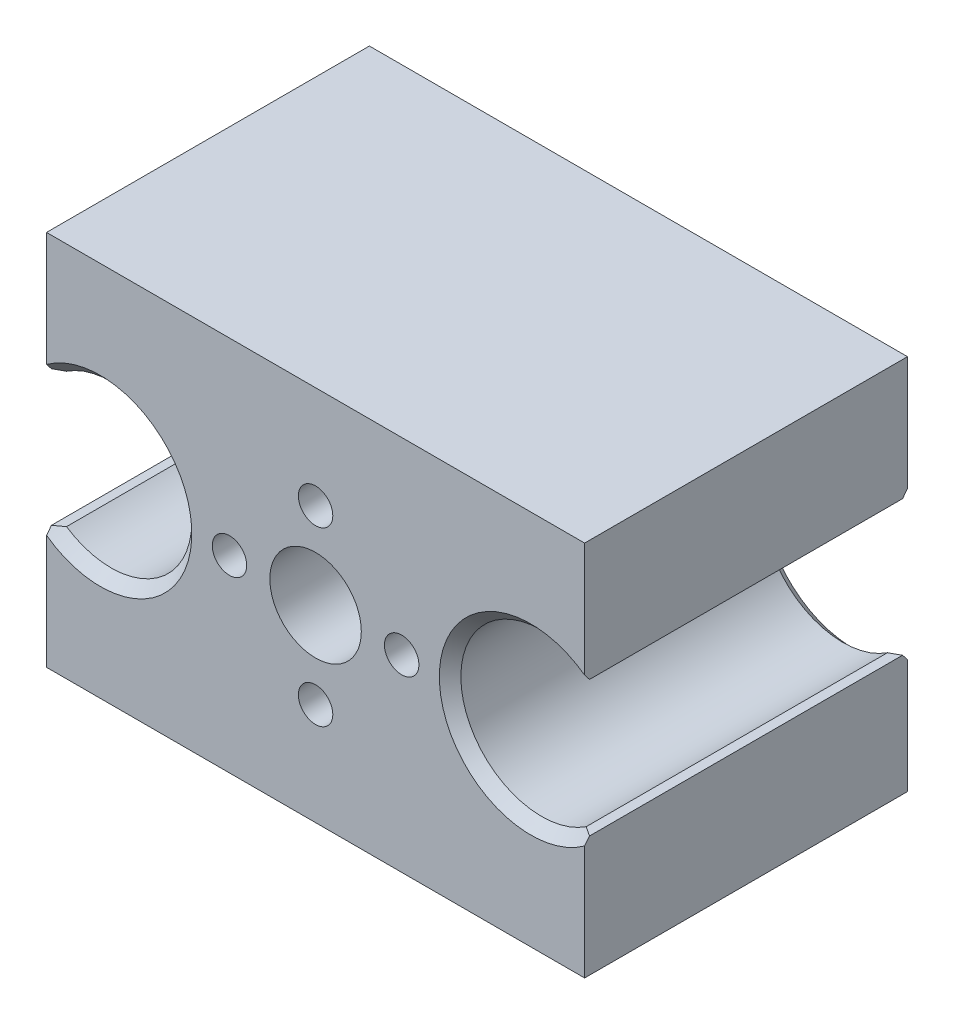
SolidWorks part; units mm, degrees
ref_plane "前视基准面" through (0, 0, 0) normal (0, 0, 1) x (1, 0, 0)
ref_plane "上视基准面" through (0, 0, 0) normal (0, 1, 0) x (1, 0, 0)
ref_plane "右视基准面" through (0, 0, 0) normal (1, 0, 0) x (0, 0, -1)
other "Configuration Table"
sketch "草图1" plane through (0, 0, 0) normal (0, 0, 1) x (1, 0, 0)
  line L1 (-25, -17.5) -> (25, -17.5)
  line L2 (-25, -17.5) -> (-25, 17.5)
  line L3 (-25, 17.5) -> (25, 17.5)
  line L4 (25, -17.5) -> (25, 17.5)
  line L5 (-25, -17.5) -> (25, 17.5) construction
  line L6 (-25, 17.5) -> (25, -17.5) construction
  point P0 (0, 0)
  dimension "D1" = 50
  dimension "D2" = 35
extrude "凸台-拉伸1" add sketch "草图1" along normal blind 30
hole_wizard "光轴孔" positions "草图2" profile "草图3" legacy end condition through all
sketch "草图2" plane through (0, 0, 30) normal (0, 0, 1) x (1, 0, 0)
  point P0 (0, 0)
sketch "草图3" plane through (0, 0, 30) normal (1, 0, 0) x (0, -1, 0)
  line L0 (0, 0) -> (0, 30)
  line L1 (0, 30) -> (4.25, 30)
  line L2 (4.25, 30) -> (4.25, 0)
  line L3 (4.25, 0) -> (0, 0)
  line L4 (0, 110) -> (0, -10) construction
  dimension "直径" = 8.5
  dimension "深度" = 30
hole_wizard "光轴座螺丝孔" positions "草图4" profile "草图5" legacy end condition through all
sketch "草图4" plane through (0, 0, 30) normal (0, 0, 1) x (1, 0, 0)
  point P0 (8, 0)
  point P4 (0, 8)
  point P6 (-8, 0)
  point P8 (0, -8)
  dimension "D1" = 8
  dimension "D2" = 8
  dimension "D3" = 8
  dimension "D4" = 8
sketch "草图5" plane through (8, 0, 30) normal (1, 0, 0) x (0, -1, 0)
  line L0 (0, 0) -> (0, 30)
  line L1 (0, 30) -> (1.6, 30)
  line L2 (1.6, 30) -> (1.6, 0)
  line L3 (1.6, 0) -> (0, 0)
  line L4 (0, 110) -> (0, -10) construction
  dimension "直径" = 3.2
  dimension "深度" = 30
hole_wizard "直线轴承座孔" positions "草图6" profile "草图7" legacy end condition through all
sketch "草图6" plane through (0, 0, 30) normal (0, 0, 1) x (1, 0, 0)
  point P0 (20, 0)
  point P2 (-20, 0)
  dimension "D1" = 20
  dimension "D2" = 20
sketch "草图7" plane through (20, 0, 30) normal (1, 0, 0) x (0, -1, 0)
  line L0 (0, 0) -> (0, 30)
  line L1 (0, 30) -> (7.5, 30)
  line L2 (7.5, 30) -> (7.5, 0)
  line L3 (7.5, 0) -> (0, 0)
  line L4 (0, 110) -> (0, -10) construction
  dimension "直径" = 15
  dimension "深度" = 30
chamfer "倒角1" distance 1 angle 45 8 edges at (25, -5.5902, 15) (12.5, 0, 30) (25, 5.5902, 15) (12.5, 0, 0) (-12.5, 0, 30) (-12.5, 0, 0) (-25, 5.5902, 15) (-25, -5.5902, 15) first distance on face at (18.75, 0, 15) first distance on face at (-18.75, 0, 15)
